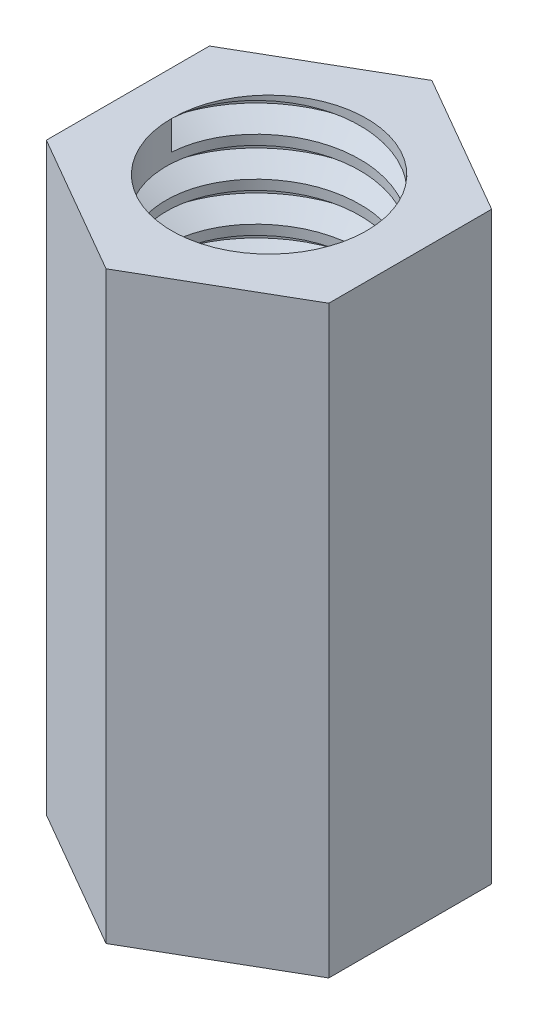
SolidWorks part; units mm, degrees
ref_plane "Front Plane" through (0, 0, 0) normal (0, 0, 1) x (1, 0, 0)
ref_plane "Top Plane" through (0, 0, 0) normal (0, 1, 0) x (1, 0, 0)
ref_plane "Right Plane" through (0, 0, 0) normal (1, 0, 0) x (0, 0, -1)
sketch "Sketch1" plane through (0, 0, 0) normal (0, 1, 0) x (1, 0, 0)
  line L0 (13.7368, -0.7955) -> (15.1868, 0.0416)
  line L1 (15.1868, 0.0416) -> (15.1868, 1.7136)
  line L2 (15.1868, 1.7136) -> (13.7348, 2.5519)
  line L3 (13.7348, 2.5519) -> (12.2868, 1.7159)
  line L4 (12.2868, 1.7159) -> (12.2868, 0.0416)
  line L5 (12.2868, 0.0416) -> (13.7368, -0.7955)
  dimension "D1" = 2.9
  dimension "D2" = 60
  dimension "D3" = 120
  dimension "D4" = 120
  dimension "D5" = 2.9
  dimension "D6" = 1.672
  dimension "D7" = 1.6743
extrude "Boss-Extrude1" add sketch "Sketch1" along normal blind 6
sketch "Sketch2" plane through (0, 6, 0) normal (0, 1, 0) x (1, 0, 0)
  circle A0 centre (13.7368, 0.8788) radius 1
  dimension "D1" = 2
extrude "Cut-Extrude1" cut sketch "Sketch2" against normal blind 10
thread "Thread1" pitch 0.4 method cut profile "Thread Profile1" start angle 0, offset 0, length 10, pitch 0.4, diameter 2
ref_plane "Plane1" through (12.7368, 6, -0.8788) normal (0, 0, 1) x (-1, 0, 0)
sketch "Thread Profile1" plane through (12.7368, 6, -0.8788) normal (0, 0, 1) x (-1, 0, 0)
  line L0 (0, 0) -> (0, 0.4) construction
  line L1 (0, 0) -> (0.2165, 0.125)
  line L2 (0.2165, 0.125) -> (0.2165, 0.175)
  line L3 (0.2165, 0.175) -> (0, 0.3)
  line L4 (0.2165, 0.15) -> (0, 0.15) construction
  line L11 (0, 0) -> (0, 0.3)
  point P2 (0, 0)
  dimension "Pitch" = 0.4
  dimension "Profile_Angle" = 60
  dimension "Profile_Land" = 0.05
  dimension "Profile_Height" = 0.2165
